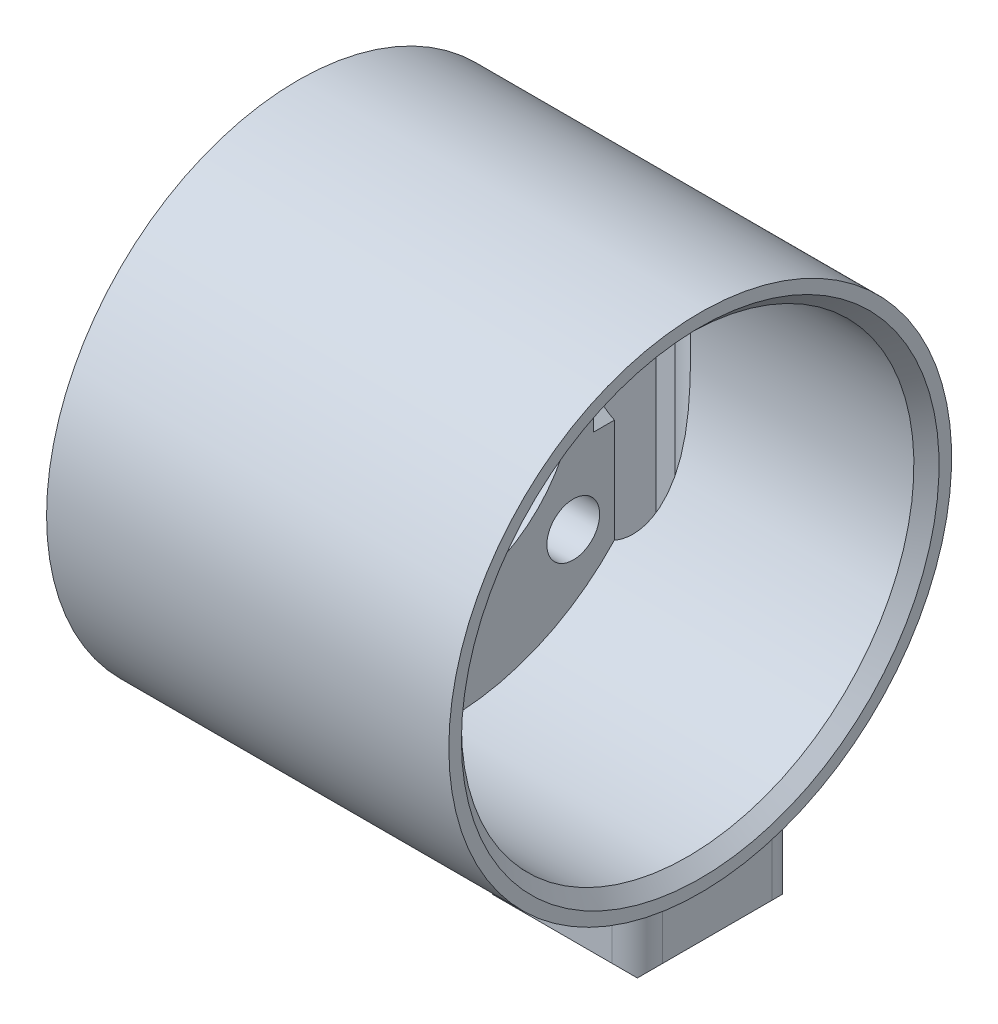
SolidWorks part; units mm, degrees
ref_plane "前视基准面" through (0, 0, 0) normal (0, 0, 1) x (1, 0, 0)
ref_plane "上视基准面" through (0, 0, 0) normal (0, 1, 0) x (1, 0, 0)
ref_plane "右视基准面" through (0, 0, 0) normal (1, 0, 0) x (0, 0, -1)
sketch "草图1" plane through (0, 0, 0) normal (1, 0, 0) x (0, 0, -1)
  circle A0 centre (0, 0) radius 20
  dimension "D1" = 40
extrude "凸台-拉伸1" add sketch "草图1" along normal blind 5
sketch "草图2" plane through (5, 0, 0) normal (1, 0, 0) x (0, 0, -1)
  line L1 (-3.15, -3.15) -> (3.15, -3.15)
  line L2 (-3.15, -3.15) -> (-3.15, 3.15)
  line L3 (-3.15, 3.15) -> (3.15, 3.15)
  line L4 (3.15, -3.15) -> (3.15, 3.15)
  line L5 (-3.15, -3.15) -> (3.15, 3.15) construction
  line L6 (-3.15, 3.15) -> (3.15, -3.15) construction
  point P0 (0, 0)
  dimension "D1" = 6.3
  dimension "D2" = 6.3
extrude "切除-拉伸1" cut sketch "草图2" against normal blind 5
sketch "草图4" plane through (0, 0, 0) normal (-1, 0, 0) x (0, 0, 1)
  circle A0 centre (0, 0) radius 20
  circle A1 centre (0, 0) radius 10
  dimension "D1" = 20
extrude "凸台-拉伸2" add sketch "草图4" along normal blind 7
sketch "草图3" plane through (0, 0, 0) normal (-1, 0, 0) x (0, 0, 1)
  line L0 (0, 0) -> (20, 0) construction
  line L1 (0, 0) -> (21.8171, -21.8171) construction
  circle A0 centre (0, 0) radius 14 construction
  circle A3 centre (9.8995, -9.8995) radius 2.1
  circle A4 centre (0, 0) radius 14 construction
  circle A5 centre (-9.8995, -9.8995) radius 2.1
  circle A6 centre (0, 0) radius 14 construction
  circle A7 centre (-9.8995, 9.8995) radius 2.1
  circle A8 centre (0, 0) radius 14 construction
  circle A9 centre (9.8995, 9.8995) radius 2.1
  point P22 (0, 0)
  dimension "D1" = 28
  dimension "D2" = 4.2
  dimension "D3" = 45
  dimension "D4" = 4
extrude "切除-拉伸2" cut sketch "草图3" against normal blind 20 and the other way blind 20
sketch "草图5" plane through (5, 0, 0) normal (1, 0, 0) x (0, 0, -1)
  line L1 (15.5, -3) -> (12.5, -3)
  line L2 (15.5, -3) -> (15.5, 3)
  line L3 (15.5, 3) -> (12.5, 3)
  line L4 (12.5, -3) -> (12.5, 3)
  line L5 (15.5, -3) -> (12.5, 3) construction
  line L6 (15.5, 3) -> (12.5, -3) construction
  point P0 (14, 0)
  dimension "D1" = 14
  dimension "D2" = 3
  dimension "D3" = 6
extrude "切除-拉伸3" cut sketch "草图5" against normal blind 13
chamfer "倒角1" distance 1 angle 45 4 edges at (-7, 3, -14) (-7, 0, -15.5) (-7, -3, -14) (-7, 0, -12.5)
sketch "草图6" plane through (-7, 0, 0) normal (-1, 0, 0) x (0, 0, 1)
  circle A0 centre (0, 0) radius 20
  circle A1 centre (0, 0) radius 18
  dimension "D1" = 40
  dimension "D2" = 36
extrude "凸台-拉伸3" add sketch "草图6" along normal blind 20
chamfer "倒角2" distance 1 angle 45 1 edges at (-27, 0, 18)
sketch "草图7" plane through (5, 0, 0) normal (1, 0, 0) x (0, 0, -1)
  circle A0 centre (-9.8995, 9.8995) radius 4.25
  circle A1 centre (9.8995, 9.8995) radius 4.25
  circle A2 centre (9.8995, -9.8995) radius 4.25
  circle A3 centre (-9.8995, -9.8995) radius 4.25
  point P12 (0, 0)
  dimension "D1" = 8.5
  dimension "D2" = 4
extrude "切除-拉伸4" cut sketch "草图7" against normal blind 2
sketch "草图8" plane through (0, 0, 0) normal (0, 1, 0) x (1, 0, 0)
  line L0 (5, -20) -> (5, 20) construction
  circle A0 centre (-6, 16) radius 0.5
  dimension "D3" = 1
  dimension "D1" = 5
  dimension "D2" = 16
extrude "切除-拉伸6" cut sketch "草图8" against normal blind 30
sketch "草图9" plane through (0, 0, 0) normal (0, -1, 0) x (1, 0, 0)
  line L1 (-7, -17) -> (-5, -17)
  line L2 (-7, -17) -> (-7, -18)
  line L3 (-7, -18) -> (-5, -18)
  line L4 (-5, -17) -> (-5, -18)
  arc A0 (-6.5, -16) -> (-6, -15.5) centre (-6, -16) ccw construction
  circle A1 centre (-6, -16) radius 0.5 construction
  dimension "D1" = 1
  dimension "D2" = 2
  dimension "D3" = 1
  dimension "D4" = 1
extrude "凸台-拉伸4" add sketch "草图9" along normal blind 20
sketch "草图10" plane through (0, -20, 0) normal (0, -1, 0) x (1, 0, 0)
  line L1 (-13, -23) -> (1, -23)
  line L2 (-13, -23) -> (-13, -9)
  line L3 (-13, -9) -> (1, -9)
  line L4 (1, -23) -> (1, -9)
  line L5 (-13, -23) -> (1, -9) construction
  line L6 (-13, -9) -> (1, -23) construction
  circle A0 centre (-6, -16) radius 3
  point P0 (-6, -16)
  dimension "D3" = 6
  dimension "D1" = 14
  dimension "D2" = 14
extrude "凸台-拉伸5" add sketch "草图10" against normal blind 3
sketch "草图11" plane through (-13, 0, 0) normal (-1, 0, 0) x (0, 0, 1)
  line L1 (-23, -17) -> (-10.5357, -17)
  line L2 (-23, -17) -> (-23, 3)
  line L3 (-23, 3) -> (-19.7737, 3)
  arc A0 (-19.7737, 3) -> (-10.5357, -17) centre (0, 0) ccw
  dimension "D1" = 40
  dimension "D3" = 20
extrude "凸台-拉伸6" add sketch "草图11" against normal blind 14
sketch "草图12" plane through (0, -20, 0) normal (0, -1, 0) x (1, 0, 0)
  line L0 (-13, -23) -> (1, -23) construction
  line L1 (-1, -20) -> (-6, -20)
  line L2 (-1, -20) -> (-1, -15)
  line L3 (-1, -15) -> (-6, -15)
  line L4 (-6, -20) -> (-6, -15)
  line L5 (1, -23) -> (1, -9) construction
  dimension "D1" = 5
  dimension "D2" = 5
  dimension "D3" = 3
  dimension "D4" = 2
extrude "切除-拉伸7" cut sketch "草图12" against normal blind 22
sketch "草图13" plane through (0, -17, 0) normal (0, -1, 0) x (1, 0, 0)
  circle A0 centre (-6, -16) radius 3
  dimension "D1" = 6
extrude "切除-拉伸8" cut sketch "草图13" against normal blind 3 and the other way blind 20
sketch "草图14" plane through (-7, 0, 0) normal (-1, 0, 0) x (0, 0, 1)
  line L0 (-16.5, -4) -> (-16.5, 4) construction
  line L1 (-16.5, 2) -> (-14, 2)
  line L2 (-16.5, 2) -> (-16.5, -4)
  line L3 (-16.5, -4) -> (-14, -4)
  line L4 (-14, 2) -> (-14, -4)
  line L5 (-11.5, -4) -> (-16.5, -4) construction
  dimension "D1" = 6
sketch "草图15" plane through (-7, 0, 0) normal (-1, 0, 0) x (0, 0, 1)
  line L0 (-14, 2) -> (-14, -4) construction
  line L1 (-16.5, 2) -> (-14, 2)
  line L2 (-16.5, 2) -> (-16.5, -3)
  line L3 (-16.5, -3) -> (-14, -3)
  line L4 (-14, 2) -> (-14, -3)
  line L5 (-15, -3) -> (-12.5, -3) construction
extrude "切除-拉伸10" [suppressed] cut sketch "草图15" against normal blind 4
sketch "草图16" plane through (-7, 0, 0) normal (-1, 0, 0) x (0, 0, 1)
  line L0 (-16.5, -4) -> (-14, -4) construction
  line L1 (-16.5, 2) -> (-15, 2)
  line L2 (-16.5, 2) -> (-16.5, -4)
  line L3 (-16.5, -4) -> (-15, -4)
  line L4 (-15, 2) -> (-15, -4)
  dimension "D1" = 1.5
extrude "切除-拉伸11" cut sketch "草图16" against normal blind 4
chamfer "倒角3" [suppressed] distance 2.5 angle 45
chamfer "倒角4" [suppressed] distance 2.5 angle 45
chamfer "倒角5" distance 2.5 angle 45 1 edges at (-1, -9, -20)
fillet "圆角1" radius 3 1 edges at (-6, 3, -23)
sketch "草图17" plane through (0, -20, 0) normal (0, -1, 0) x (1, 0, 0)
  line L1 (-12.35, -22.35) -> (0.35, -22.35)
  line L2 (-12.35, -22.35) -> (-12.35, -9.65)
  line L3 (-12.35, -9.65) -> (0.35, -9.65)
  line L4 (0.35, -22.35) -> (0.35, -9.65)
  line L5 (-12.35, -22.35) -> (0.35, -9.65) construction
  line L6 (-12.35, -9.65) -> (0.35, -22.35) construction
  circle A0 centre (-6, -16) radius 3
  point P0 (-6, -16)
  dimension "D3" = 6
  dimension "D1" = 12.7
  dimension "D2" = 12.7
extrude "凸台-拉伸7" add sketch "草图17" along normal blind 20
sketch "草图18" plane through (0, -20, 0) normal (0, -1, 0) x (1, 0, 0)
  line L1 (1, -9) -> (-13, -9)
  line L2 (1, -9) -> (1, 0)
  line L3 (1, 0) -> (-13, 0)
  line L4 (-13, -9) -> (-13, 0)
  dimension "D1" = 14
  dimension "D2" = 0
extrude "凸台-拉伸8" add sketch "草图18" against normal blind 2
sketch "草图19" plane through (1, 0, 0) normal (1, 0, 0) x (0, 0, -1)
  line L1 (9.6254, -18.3944) -> (8.1234, -18.3944)
  line L2 (9.6254, -18.3944) -> (9.6254, -17.4426)
  line L3 (9.6254, -17.4426) -> (8.1234, -17.4426)
  line L4 (8.1234, -18.3944) -> (8.1234, -17.4426)
extrude "凸台-拉伸9" add sketch "草图19" against normal blind 14
chamfer "倒角6" distance 4 angle 45 1 edges at (-13, -13.0384, -15.1658)
chamfer "倒角7" distance 4 angle 45 1 edges at (1, -13.0384, -15.1658)
sketch "草图20" plane through (0.35, 0, 0) normal (1, 0, 0) x (0, 0, -1)
  line L0 (22.35, -20) -> (9.65, -20) construction
  line L1 (9.65, -40) -> (9.65, -20) construction
  circle A0 centre (16, -30) radius 1.65
  dimension "D1" = 3.3
  dimension "D2" = 10
  dimension "D3" = 6.35
extrude "切除-拉伸12" cut sketch "草图20" against normal blind 16
chamfer "倒角8" distance 2 angle 45 4 edges at (-6, -40, -9.65) (0.35, -40, -16) (-6, -40, -22.35) (-12.35, -40, -16)
chamfer "倒角9" distance 2 angle 45 1 edges at (-4.5858, -14, -15)
chamfer "倒角10" [suppressed] distance 2 angle 45
chamfer "倒角11" distance 2 angle 45 1 edges at (-3.5505, -20, -17.7321)
fillet "圆角2" radius 3 1 edges at (-6, -14, -16)
fillet "圆角3" radius 3 1 edges at (-6, -16.5, -19)
fillet "圆角4" radius 2 4 edges at (0.35, -29, -22.35) (-12.35, -29, -22.35) (-12.35, -29, -9.65) (0.35, -29, -9.65)
sketch "草图21" plane through (5, 0, 0) normal (1, 0, 0) x (0, 0, -1)
  line L0 (14, 2) -> (14, -4) construction
  circle A0 centre (14, 0) radius 2.5
  dimension "D1" = 5
extrude "切除-拉伸13" cut sketch "草图21" against normal blind 15
sketch "草图22" plane through (0, -40, 0) normal (0, -1, 0) x (1, 0, 0)
  circle A0 centre (-6, -16) radius 3
extrude "切除-拉伸14" cut sketch "草图22" against normal blind 42
mirror "镜向1" about plane through (5, 0, 0) normal (1, 0, 0) of bodies 127
sketch "草图23" plane through (-27, 0, 0) normal (-1, 0, 0) x (0, 0, 1)
  line L1 (-47.1038, 28.8744) -> (50.3525, 28.8744)
  line L2 (-47.1038, 28.8744) -> (-47.1038, -49.7156)
  line L3 (-47.1038, -49.7156) -> (50.3525, -49.7156)
  line L4 (50.3525, 28.8744) -> (50.3525, -49.7156)
extrude "切除-拉伸15" cut sketch "草图23" against normal blind 32
